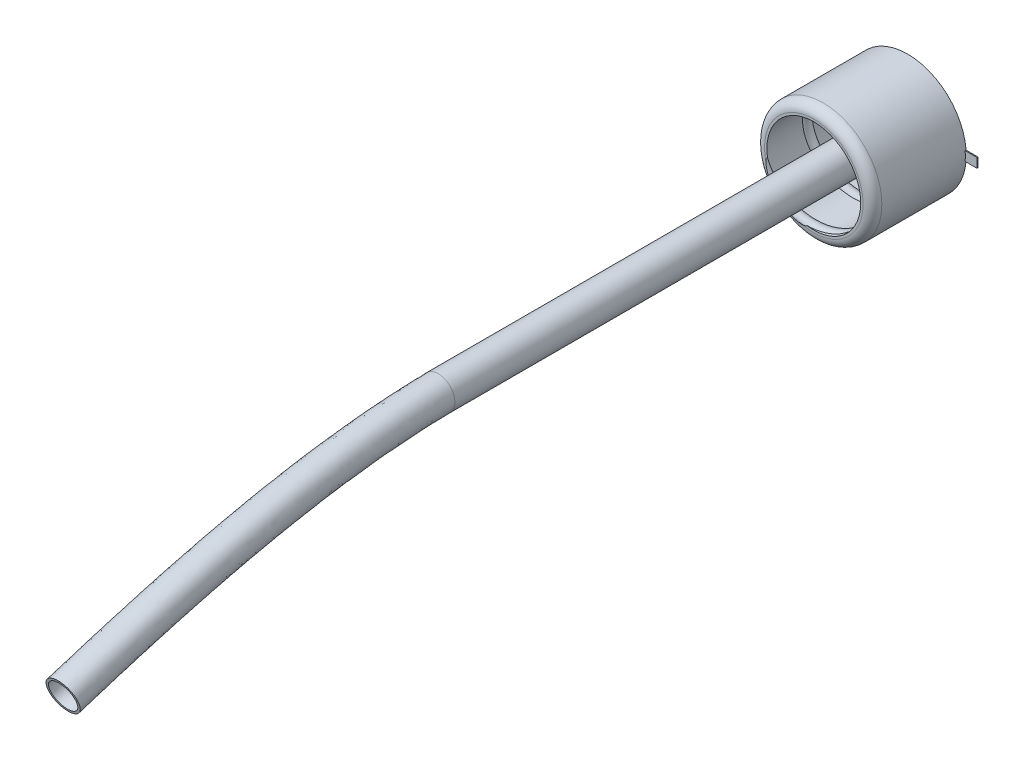
SolidWorks part; units mm, degrees
ref_plane "Front Plane" through (0, 0, 0) normal (0, 0, 1) x (1, 0, 0)
ref_plane "Top Plane" through (0, 0, 0) normal (0, 1, 0) x (1, 0, 0)
ref_plane "Right Plane" through (0, 0, 0) normal (1, 0, 0) x (0, 0, -1)
sketch "Sketch1" plane through (0, 0, 0) normal (0, 0, 1) x (1, 0, 0)
  circle A0 centre (0, 0) radius 15.875
  dimension "D1" = 31.75
extrude "Boss-Extrude1" add sketch "Sketch1" along normal blind 25.4 contours A0
shell "Shell1" thickness 3.175 removed face at (15.875, 0, 25.4)
sketch "Sketch2" plane through (0, 0, 3.175) normal (0, 0, 1) x (1, 0, 0)
  circle A0 centre (0, 0) radius 12.7
curve "Helix/Spiral1" pitch 12.7 height 47.625 turns 3.75
sketch "Sketch3" plane through (0, 0, 3.175) normal (0, 0, 1) x (1, 0, 0)
sweep "Cut-Sweep1" cut path "Helix/Spiral1" align with end faces yes circular profile diameter 2.54 parameters "D3"=2.54
fillet "Fillet1" radius 2.54 1 edges at (15.875, 0, 25.4)
sketch "Sketch4" plane through (0, 0, 0) normal (0, 0, -1) x (-1, 0, 0)
  line L1 (-19.05, 1.27) -> (-12.7, 1.27)
  line L2 (-19.05, 1.27) -> (-19.05, -1.27)
  line L3 (-19.05, -1.27) -> (-12.7, -1.27)
  line L4 (-12.7, 1.27) -> (-12.7, -1.27)
  line L5 (-19.05, 1.27) -> (-12.7, -1.27) construction
  line L6 (-19.05, -1.27) -> (-12.7, 1.27) construction
  line L7 (19.05, 1.27) -> (12.7, 1.27)
  line L8 (19.05, 1.27) -> (19.05, -1.27)
  line L9 (19.05, -1.27) -> (12.7, -1.27)
  line L10 (12.7, 1.27) -> (12.7, -1.27)
  line L11 (19.05, 1.27) -> (12.7, -1.27) construction
  line L12 (19.05, -1.27) -> (12.7, 1.27) construction
  circle A1 centre (0, 0) radius 15.875
  point P1 (-15.875, 0)
  point P8 (15.875, 0)
  circle M8 centre (0, 0) radius 15.875
  dimension "D3" = 31.75
  dimension "D1" = 6.35
  dimension "D2" = 2.54
extrude "Boss-Extrude2" add sketch "Sketch4" against normal blind 0.254 contours L9 L8 L7 M8 | L2 L3 L1 M8
sketch "Sketch38" plane through (0, 0, 0) normal (1, 0, 0) x (0, 0, -1)
  line L0 (0, 0) -> (-127, 0)
  spline S0 degree 3 poles (-127, 0) (-161.9407, -0.6808) (-195.619, -9.905) (-228.6, -20.32) knots 0 0 0 0 1 1 1 1
  dimension "D1" = 127
  dimension "D2" = 6.35
  dimension "D3" = 50.8
  dimension "D4" = 6.35
  dimension "D5" = 25.4
  dimension "D6" = 7.62
  dimension "D7" = 25.4
sweep "Sweep1" add path "Sketch38" circular profile diameter 8.89 parameters "D3"=8.89
ref_plane "Plane1" through (0, -67.4856, 213.7057) normal (0, -0.3011, 0.9536) x (1, 0, 0)
sketch "Sketch59" plane through (0, -67.4856, 213.7057) normal (0, -0.3011, 0.9536) x (1, 0, 0)
  line L0 (-4.445, 49.4614) -> (4.445, 49.4614)
  line L1 (0, 53.9064) -> (0, 45.0164)
  circle A1 centre (0, 49.4614) radius 4.445 construction
  circle A2 centre (0, 49.4614) radius 3.175
  dimension "D1" = 6.35
sketch "Sketch60" plane through (0, 0, 0) normal (1, 0, 0) x (0, 0, -1)
  line L2 (0, 0) -> (-127, 0)
  line L3 (-2.54, 0) -> (-127, 0)
  spline S2 degree 3 poles (624.7246, -1829.7585) (-213.2759, 2060.3193) (-328.5634, -2118.0988) (-963.6998, 1796.9914) knots -5.329129 -5.329129 -5.329129 -5.329129 7.673178 7.673178 7.673178 7.673178 only from (-127, 0) to (-228.6, -20.32)
  spline S3 degree 3 poles (-127, 0) (-161.9407, -0.6808) (-195.619, -9.905) (-228.6, -20.32) knots 0 0 0 0 1 1 1 1
  dimension "D1" = 0
sweep "Cut-Sweep2" cut path "Sketch60" circular profile diameter 7.62 parameters "D3"=7.62
